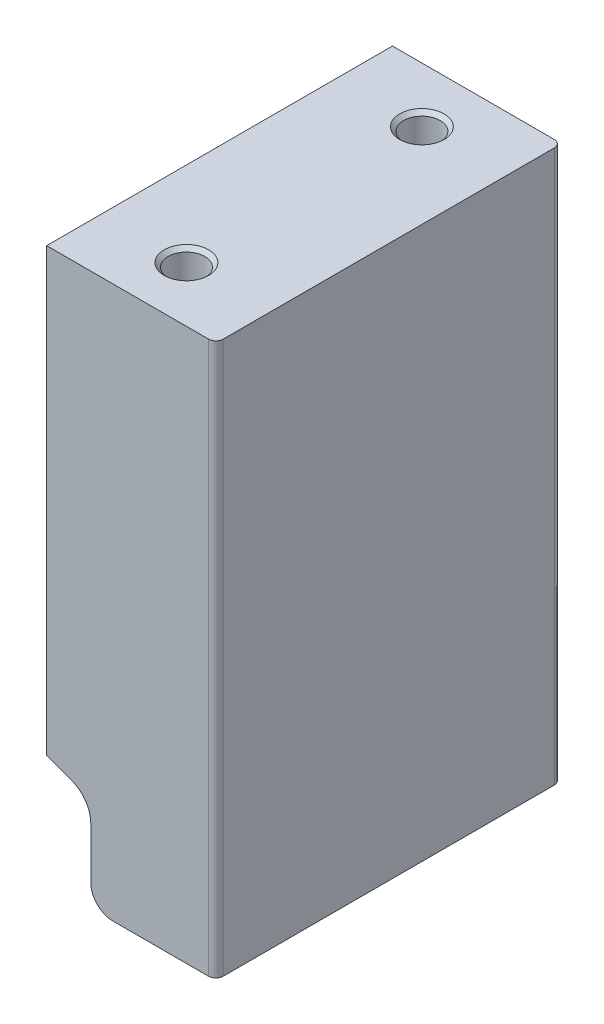
SolidWorks part; units mm, degrees
material "K110"
ref_plane "Front Plane" through (0, 0, 0) normal (0, 0, 1) x (1, 0, 0)
ref_plane "Top Plane" through (0, 0, 0) normal (0, 1, 0) x (1, 0, 0)
ref_plane "Right Plane" through (0, 0, 0) normal (1, 0, 0) x (0, 0, -1)
sketch "Sketch1" plane through (0, 0, 0) normal (0, 1, 0) x (1, 0, 0)
  line L1 (-11.5, -23.5) -> (11.5, -23.5)
  line L2 (-11.5, -23.5) -> (-11.5, 23.5)
  line L3 (-11.5, 23.5) -> (11.5, 23.5)
  line L4 (11.5, -23.5) -> (11.5, 23.5)
  line L5 (-11.5, -23.5) -> (11.5, 23.5) construction
  line L6 (-11.5, 23.5) -> (11.5, -23.5) construction
  point P0 (0, 0)
  dimension "D1" = 23
  dimension "D2" = 47
extrude "Boss-Extrude1" add sketch "Sketch1" against normal blind 75
sketch "Sketch2" plane through (0, 0, 23.5) normal (0, 0, 1) x (1, 0, 0)
  line L0 (-11.5, 0) -> (11.5, 0) construction
  line L1 (-11.5, -75) -> (-5.5, -75) construction
  line L2 (-11.5, -75) -> (-11.5, -61) construction
  line L3 (-11.5, -61) -> (-9.5, -61) construction
  line L4 (-5.5, -75) -> (-5.5, -65) construction
  line L5 (11.5, -75) -> (11.5, 0) construction
  line L6 (-8.1319, -61.2412) -> (-11.5, -60.0153)
  line L7 (-11.5, -75) -> (-11.5, 0) construction
  line L8 (-5.5, -65) -> (-5.5, -75)
  line L9 (-5.5, -75) -> (-11.5, -75)
  line L10 (-11.5, -75) -> (-11.5, -60.0153)
  arc A0 (-9.5, -61) -> (-5.5, -65) centre (-9.5, -65) cw construction
  arc A1 (-5.5, -65) -> (-8.1319, -61.2412) centre (-9.5, -65) ccw
  dimension "D3" = 4
  dimension "D1" = 61
  dimension "D2" = 17
  dimension "D4" = 2
  dimension "D5" = 20
extrude "Cut-Extrude1" cut sketch "Sketch2" against normal up to next
fillet "Fillet1" radius 3 1 edges at (-5.5, -75, 0)
fillet "Fillet2" radius 1 2 edges at (11.5, -37.5, -23.5) (11.5, -37.5, 23.5)
hole_wizard "M6 Tapped Hole1" positions "Sketch5" profile "Sketch4" tap size "M6" standard "ISO"
sketch "Sketch5" plane through (0, 0, 0) normal (0, 1, 0) x (1, 0, 0)
  line L0 (10.5, 23.5) -> (-11.5, 23.5) construction
  line L1 (-11.5, -23.5) -> (10.5, -23.5) construction
  point P0 (0, 16)
  point P2 (0, -16)
  dimension "D1" = 7.5
  dimension "D2" = 7.5
sketch "Sketch4" plane through (0, 0, -16) normal (1, 0, 0) x (0, 0, 1)
  line L0 (0, 0) -> (0, 18.5022)
  line L1 (0, 18.5022) -> (2.5, 17)
  line L2 (2.5, 17) -> (2.5, 0.525)
  line L3 (2.5, 0.525) -> (3.025, 0)
  line L5 (3.025, 0) -> (0, 0)
  line L6 (-2.5, 0.525) -> (-3.025, 0) construction
  line L10 (0, 18.5022) -> (-2.5, 17) construction
  line L11 (0, -6.35) -> (0, 107.95) construction
  dimension "Tap Drill Dia." = 5
  dimension "Tap Drill Depth" = 17
  dimension "Near C'Sink Dia." = 6.05
  dimension "Near C'Sink Angle" = 90
  dimension "Drill Angle" = 118
cosmetic thread "Hole Thread1" parameters "D1"=12, "D2"=6
cosmetic thread "Hole Thread2" parameters "D1"=12, "D2"=6
ref_plane "Plane1" through (0, -50, 0) normal (0, 1, 0) x (1, 0, 0)
sketch "Sketch6" plane through (0, -50, 0) normal (0, 1, 0) x (1, 0, 0)
  line L0 (-11.5, 23.5) -> (-11.5, -23.5)
  line L1 (-11.5, 23.5) -> (-11.5, -23.5)
  line L2 (-11.5, -23.5) -> (10.5, -23.5)
  line L3 (-11.5, -23.5) -> (10.5, -23.5)
  line L4 (11.5, -22.5) -> (11.5, 22.5)
  line L5 (11.5, -22.5) -> (11.5, 22.5)
  line L6 (10.5, 23.5) -> (-11.5, 23.5)
  line L7 (10.5, 23.5) -> (-11.5, 23.5)
  arc A0 (10.5, -23.5) -> (11.5, -22.5) centre (10.5, -22.5) ccw
  arc A1 (10.5, -23.5) -> (11.5, -22.5) centre (10.5, -22.5) ccw
  arc A2 (11.5, 22.5) -> (10.5, 23.5) centre (10.5, 22.5) ccw
  arc A3 (11.5, 22.5) -> (10.5, 23.5) centre (10.5, 22.5) ccw
